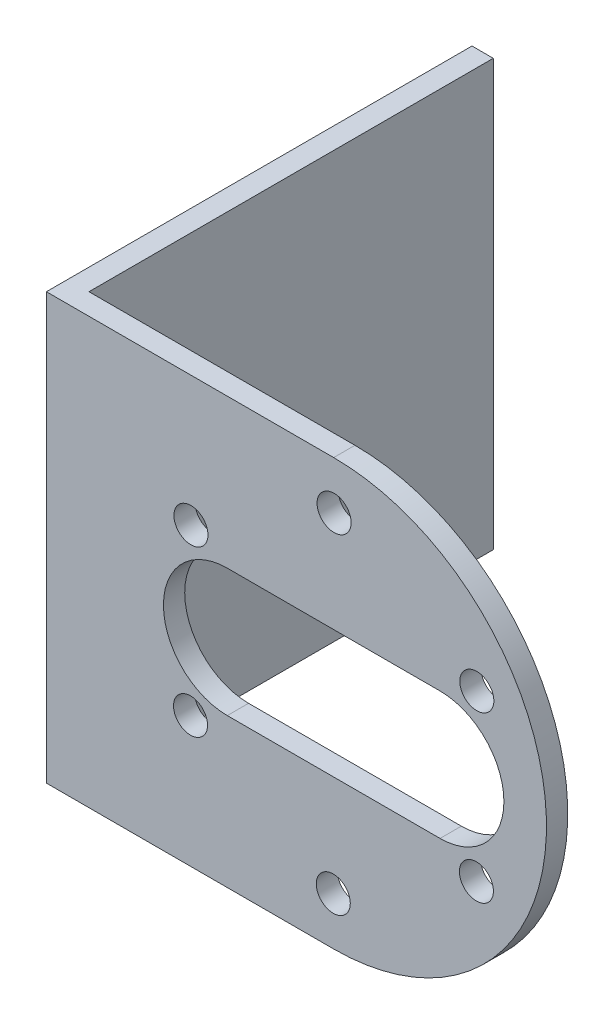
SolidWorks part; units mm, degrees
ref_plane "Front Plane" through (0, 0, 0) normal (0, 0, 1) x (1, 0, 0)
ref_plane "Top Plane" through (0, 0, 0) normal (0, 1, 0) x (1, 0, 0)
ref_plane "Right Plane" through (0, 0, 0) normal (1, 0, 0) x (0, 0, -1)
sketch "草图1" plane through (0, 0, 0) normal (1, 0, 0) x (0, 0, -1)
  line L1 (20, 20) -> (-20, 20)
  line L2 (20, 20) -> (20, -20)
  line L3 (20, -20) -> (-20, -20)
  line L4 (-20, 20) -> (-20, -20)
  line L5 (20, 20) -> (-20, -20) construction
  line L6 (20, -20) -> (-20, 20) construction
  point P0 (0, 0)
  dimension "D1" = 40
  dimension "D2" = 40
extrude "凸台-拉伸1" add sketch "草图1" along normal blind 2
ref_plane "基准面1" through (0, 0, 20) normal (0, 0, 1) x (1, 0, 0)
sketch "草图3" plane through (0, 0, 20) normal (0, 0, 1) x (1, 0, 0)
  line L0 (0, 20) -> (27, 20)
  line L1 (-25.8231, 17.3294) -> (-48.8231, 17.3294)
  line L2 (-48.8231, 17.3294) -> (-48.8231, -22.6706)
  line L3 (-48.8231, -22.6706) -> (-25.8231, -22.6706)
  line L4 (-48.8231, 17.3294) -> (-52.8231, 17.3294)
  line L5 (-52.8231, 17.3294) -> (-52.8231, -22.6706)
  line L6 (-52.8231, -22.6706) -> (-48.8231, -22.6706)
  line L7 (0, -20) -> (27, -20)
  line L8 (0, 20) -> (0, -20)
  line L9 (27, 23.863) -> (27, -25.1353) construction
  line L10 (37, 0) -> (17, 0) construction
  line L11 (37, -6) -> (17, -6)
  line L12 (37, 6) -> (17, 6)
  arc A0 (-25.8231, -22.6706) -> (-25.8231, 17.3294) centre (-25.8231, -2.6706) ccw
  arc A1 (27, -20) -> (27, 20) centre (27, 0) ccw
  circle A2 centre (27, 0) radius 15.5 construction
  arc A3 (37, -6) -> (37, 6) centre (37, 0) ccw
  arc A4 (17, 6) -> (17, -6) centre (17, 0) ccw
  ellipse E0 centre (27.0387, 15.5126) end of major axis (25.9073, 16.644) minor radius 1.6
  point P15 (27, 15.5)
  point P26 (27, 0)
  dimension "D5" = 20
  dimension "D6" = 20
  dimension "D7" = 20
  dimension "D1" = 27
  dimension "D2" = 4
  dimension "D3" = 40
  dimension "D4" = 23
extrude "凸台-拉伸2" add sketch "草图3" against normal blind 2 contours A1 L0 L8 L7
sketch "草图5" plane through (0, 0, 0) normal (0, 0, 1) x (1, 0, 0)
  line L6 (27, 19.5) -> (4, 19.5)
  line L7 (4, 19.5) -> (4, -20.5)
  line L8 (4, -20.5) -> (27, -20.5)
  arc A2 (27, -20.5) -> (27, 19.5) centre (27, -0.5) ccw
  ellipse E1 centre (27, 15) end of major axis (25.8686, 16.1314) minor radius 1.6
  ellipse E3 centre (13.5766, 7.25) end of major axis (12.4452, 8.3814) minor radius 1.6
  ellipse E5 centre (13.5766, -8.25) end of major axis (12.4452, -7.1186) minor radius 1.6
  ellipse E7 centre (40.4234, 7.25) end of major axis (39.292, 8.3814) minor radius 1.6
  ellipse E9 centre (40.4234, -8.25) end of major axis (39.292, -7.1186) minor radius 1.6
  ellipse E11 centre (27, -16) end of major axis (25.8686, -17.1314) minor radius 1.6
  point P0 (0, 0)
extrude "切除-拉伸1" cut sketch "草图3<4>" against normal blind 2 contours E0 region at (27.0387, 15.5126, 20)
sketch "草图3<4>" plane through (0, 0, 20) normal (0, 0, 1) x (1, 0, 0) same geometry as "草图3"
pattern_circular "阵列(圆周)1" count 6 over 360 about axis through (27, 0, 20) along (0, 0, 1) of "切除-拉伸1"
ref_plane "基准面2" through (0, 0, 20) normal (0, 0, 1) x (1, 0, 0)
extrude "切除-拉伸2" cut sketch "草图3<5>" against normal through all contours L11 A4 L12 A3
sketch "草图3<5>" plane through (0, 0, 20) normal (0, 0, 1) x (1, 0, 0) same geometry as "草图3"
